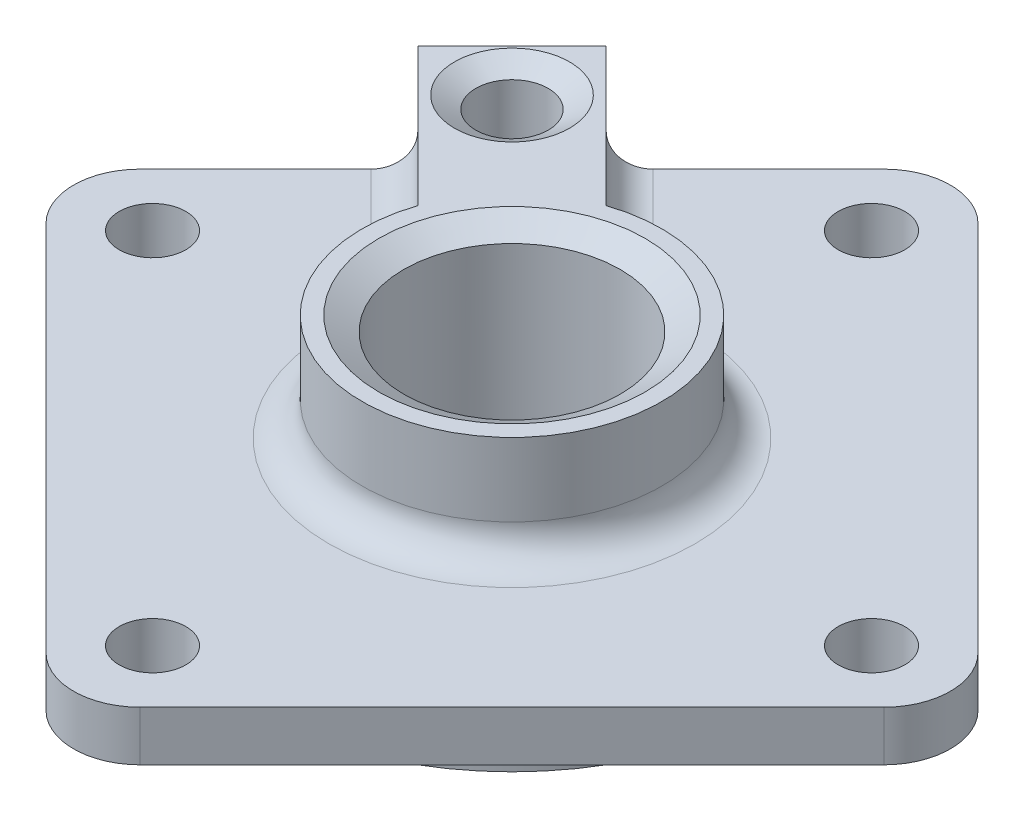
SolidWorks part; units mm, degrees
material "6061-T6 (SS)"
ref_plane "Front Plane" through (0, 0, 0) normal (0, 0, 1) x (1, 0, 0)
ref_plane "Top Plane" through (0, 0, 0) normal (0, 1, 0) x (1, 0, 0)
ref_plane "Right Plane" through (0, 0, 0) normal (1, 0, 0) x (0, 0, -1)
sketch "Sketch1" plane through (0, 0, 0) normal (0, 0, 1) x (1, 0, 0)
  line L0 (10.3187, 19.9644) -> (14.2875, 19.9644)
  line L1 (14.2875, 19.9644) -> (14.2875, 9.8044)
  line L2 (14.2875, 9.8044) -> (44.45, 9.8044)
  line L3 (44.45, 9.8044) -> (44.45, 5.0419)
  line L4 (44.45, 5.0419) -> (28.575, 5.0419)
  line L5 (28.575, 5.0419) -> (25.1206, 1.5875)
  line L6 (25.1206, 1.5875) -> (25.1206, 0)
  line L7 (25.1206, 0) -> (10.3187, 0)
  line L9 (10.3187, 0) -> (10.3187, 19.9644)
  line L10 (0, 0) -> (0, 39.3638) construction
  dimension "D1" = 3.4544
  dimension "D2" = 3.4544
  dimension "D4" = 4.7625
  dimension "D5" = 10.3187
  dimension "D6" = 14.2875
  dimension "D7" = 28.575
  dimension "D8" = 10.16
  dimension "D9" = 44.45
  dimension "D10" = 1.5875
revolve "Revolve1" add sketch "Sketch1" angle 360 about L10
sketch "Sketch2" plane through (0, 0, 0) normal (0, 1, 0) x (1, 0, 0)
  line L0 (0, 0) -> (0, 34.29) construction
  line L1 (0, 0) -> (34.29, 0) construction
  line L2 (0, 0) -> (0, -34.29) construction
  line L3 (0, 0) -> (-34.29, 0) construction
  point P15 (0, 0)
  dimension "D1" = 34.29
  dimension "D2" = 4
sketch "Sketch3" plane through (0, 0, 0) normal (0, 1, 0) x (1, 0, 0)
  line L0 (-44.45, 0) -> (0, 44.45)
  line L1 (0, 34.29) -> (0, 0) construction
  line L3 (0, 44.45) -> (44.45, 0)
  line L4 (44.45, 0) -> (0, -44.45)
  line L5 (0, -44.45) -> (-44.45, 0)
  circle A12 centre (0, 34.29) radius 3.175
  circle A13 centre (-34.29, 0) radius 3.175
  circle A14 centre (34.29, 0) radius 3.175
  circle A15 centre (0, -34.29) radius 3.175
  circle A16 centre (0, 0) radius 44.45
  circle A17 centre (0, 0) radius 44.45 construction
  circle A29 centre (0, 0) radius 31.75 construction
  point P2 (0, 0)
  point P33 (0, 0)
  dimension "D1" = 6.35
  dimension "D2" = 34.29
extrude "Cut-Extrude4" cut sketch "Sketch3" against normal through all both and the other way through all contours L5 A16 | L4 A16 | L3 A16 | L0 A16 | A13 | A12 | A14 | A15 region at (-25.9579, 0, -25.9579) region at (-25.9579, 0, 25.9579) region at (25.9579, 0, -25.9579) region at (25.9579, 0, 25.9579) region at (0, 0, -34.29) region at (-34.29, 0, 0) region at (34.29, 0, 0) region at (0, 0, 34.29)
fillet "Fillet3" radius 6.35 4 edges at (0, 7.4232, -44.45) (44.45, 7.4232, 0) (0, 7.4232, 44.45) (-44.45, 7.4232, 0)
sketch "Sketch4" plane through (0, 0, 0) normal (0, 1, 0) x (1, 0, 0)
  line L10 (0, 0) -> (-22.225, 22.225) construction
  line L29 (-4.4901, 39.9599) -> (-39.9599, 4.4901) construction
  line L30 (-22.225, 22.225) -> (-26.7151, 17.7349)
  line L31 (-26.7151, 17.7349) -> (-11.7866, 2.8063)
  line L32 (-11.7866, 2.8063) -> (-2.8063, 11.7866)
  line L33 (-2.8063, 11.7866) -> (-17.7349, 26.7151)
  line L34 (-17.7349, 26.7151) -> (-22.225, 22.225)
  circle A0 centre (0, 0) radius 10.3187 construction
  point P12 (-18.1839, 18.1839)
  dimension "D1" = 12.7
  dimension "D2" = 5.715
extrude "Boss-Extrude1" add sketch "Sketch4" along normal blind 10.16 from surface starting at face at (34.29, 9.8044, 3.175)
sketch "Sketch6" plane through (0, 19.9644, 0) normal (0, 1, 0) x (1, 0, 0)
  point P0 (-18.1839, 18.1839)
fillet "Fillet2" radius 3.175 3 edges at (10.1028, 9.8044, 10.1028) (-11.1474, 9.8044, -20.1277) (-20.1277, 9.8044, -11.1474)
chamfer "Chamfer2" distance 2.3813 angle 30 1 edges at (0, 19.9644, -10.3187) first distance on face at (0, 19.9644, -10.3187)
sketch "Sketch8" plane through (0, 0, 0) normal (0, 1, 0) x (1, 0, 0)
  line L0 (0, 0) -> (-17.0625, 17.0625) construction
  line L1 (0, 0) -> (-6.9552, 0) construction
  circle A0 centre (-17.0625, 17.0625) radius 0.7937
  dimension "D1" = 1.5875
  dimension "D2" = 45
  dimension "D3" = 24.13
extrude "Cut-Extrude3" cut sketch "Sketch8" against normal through all both and the other way through all
hole_wizard "5/16-24 Tapped Hole1" positions "Sketch6" profile "Sketch9" tap size "5/16-24" standard "ANSI Inch"
sketch "Sketch9" plane through (-18.1839, 19.9644, -18.1839) normal (1, 0, 0) x (0, 0, 1)
  line L0 (0, 0) -> (0, 14.7756)
  line L1 (0, 14.7756) -> (3.4544, 12.7)
  line L2 (3.4544, 12.7) -> (3.4544, 0)
  line L5 (3.4544, 0) -> (0, 0)
  line L10 (0, 14.7756) -> (-3.4544, 12.7) construction
  line L11 (0, -6.35) -> (0, 107.95) construction
  dimension "Tap Drill Dia." = 6.9088
  dimension "Tap Drill Depth" = 12.7
  dimension "Drill Angle" = 118
chamfer "Chamfer3" distance 2.032 angle 30 1 edges at (-18.1839, 19.9644, -14.7295) first distance on face at (-18.1839, 19.9644, -14.7295)
